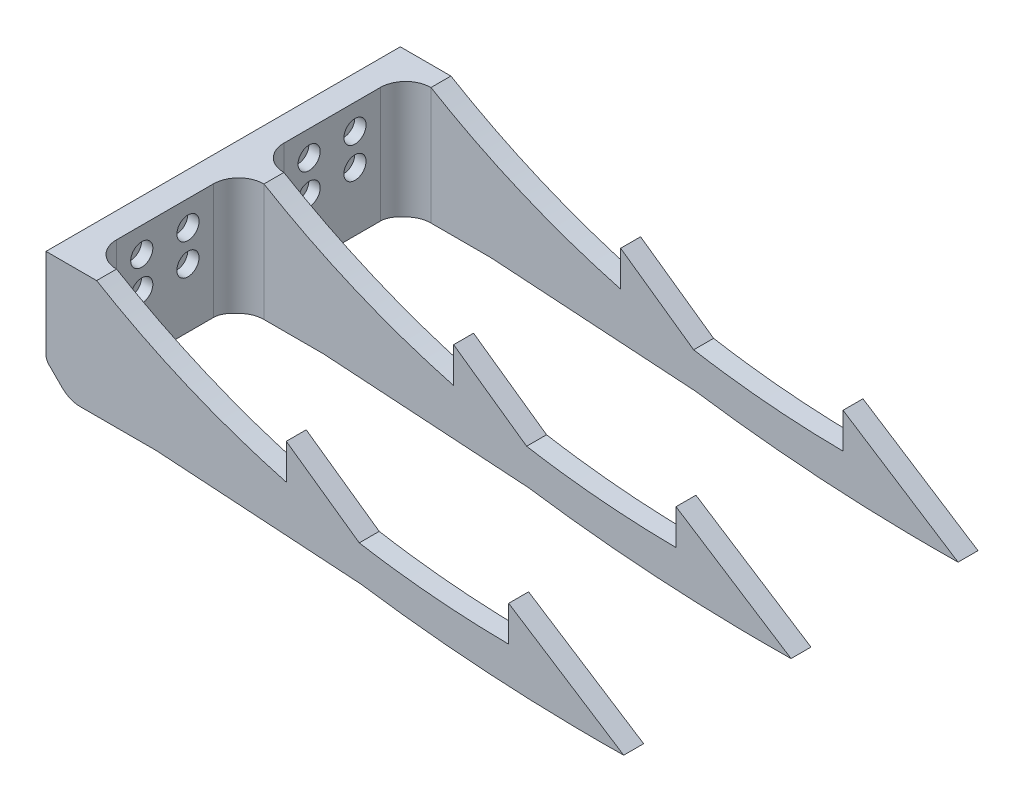
SolidWorks part; units mm, degrees
ref_plane "Front Plane" through (0, 0, 0) normal (0, 0, 1) x (1, 0, 0)
ref_plane "Top Plane" through (0, 0, 0) normal (0, 1, 0) x (1, 0, 0)
ref_plane "Right Plane" through (0, 0, 0) normal (1, 0, 0) x (0, 0, -1)
sketch "Sketch1" plane through (0, 0, 0) normal (0, 0, 1) x (1, 0, 0)
  line L0 (0, -6.35) -> (0, 6.35)
  line L1 (0, 6.35) -> (12.7, 6.35)
  line L2 (116.0939, -20.9749) -> (116.0939, -12.0849)
  line L3 (116.0939, -12.0849) -> (144.9605, -30.6605)
  line L4 (78.6103, -17.6935) -> (60.2919, -4.7804)
  line L5 (0, 12.7) -> (0, -12.7) construction
  line L6 (0, -12.7) -> (17.9605, -30.6605) construction
  line L7 (17.9605, -30.6605) -> (144.9605, -30.6605) construction
  line L8 (60.2919, -4.7804) -> (60.2919, -13.6704)
  spline S0 degree 2 poles (144.9605, -30.6605) (68.4115, -31.7178) (0, -6.35) knots 0 0 0 0.711551 0.711551 0.711551
  spline S1 degree 2 poles (116.0939, -20.9749) (96.6139, -20.8008) (78.6103, -17.6935) knots 0 0 0 0.222604 0.222604 0.222604
  spline S2 degree 3 poles (60.2919, -13.6704) (43.3593, -9.12) (27.4954, -2.4465) (12.7, 6.35) knots 0.338319 0.338319 0.338319 0.338319 0.666344 0.666344 0.666344 0.666344
  dimension "D1" = 12.7
  dimension "D2" = 12.7
  dimension "D3" = 8.89
  dimension "D4" = 8.89
  dimension "D6" = 25.4
  dimension "D8" = 25.4
  dimension "D9" = 127
extrude "Boss-Extrude1" add sketch "Sketch1" along normal blind 5
sketch "Sketch2" plane through (0, 0, 5) normal (0, 0, 1) x (1, 0, 0)
  line L0 (16.0704, -23.1077) -> (8.5569, -23.1077)
  line L1 (0, 6.35) -> (6.3316, 6.35)
  line L2 (0, 6.35) -> (0, -9.1178)
  line L3 (0, -9.1178) -> (0, -16.3764)
  line L4 (6.3316, 6.35) -> (6.3316, -8.6351)
  line L5 (27.6327, -23.1077) -> (16.0704, -23.1077)
  line L6 (6.3316, -8.6351) -> (13.8152, -11.1762)
  line L7 (4.0668, -21.2478) -> (0.6193, -17.8003)
  line L9 (79.2431, -26.4677) -> (27.6327, -23.1077)
  arc A0 (4.0668, -21.2478) -> (8.5569, -23.1077) centre (8.5569, -16.7577) ccw
  arc A2 (0, -16.3764) -> (0.6193, -17.8003) centre (2.5274, -16.1238) ccw
  parabola Q0 (13.8152, -11.1762) -> (79.2431, -26.4677) focus (76.8846, 170.0406) apex (20.4253, -13.2777)
  parabola Q1 (0, -6.35) -> (144.9605, -30.6605) focus (77.0052, 170.1195) apex (20.5192, -13.3081) construction
  parabola Q2 (0, -6.35) -> (144.9605, -30.6605) focus (77.0052, 170.1195) apex (20.5192, -13.3081) construction
  dimension "D2" = 6.35
extrude "Boss-Extrude2" add sketch "Sketch2" against normal blind 88.9
ref_plane "Plane1" through (0, 0, -39.45) normal (0, 0, 1) x (1, 0, 0)
mirror "Mirror1" about plane through (0, 0, -39.45) normal (0, 0, 1) of "Boss-Extrude1"
ref_plane "Plane2" through (0, 0, -18.495) normal (0, 0, 1) x (1, 0, 0)
mirror "Mirror3" about plane through (0, 0, -18.495) normal (0, 0, 1) of "Boss-Extrude1"
sketch "Sketch8" plane through (0, 6.35, 0) normal (0, 1, 0) x (1, 0, 0)
  line L0 (6.3316, 78.9) -> (84.5362, 78.9)
  line L1 (78.6103, 78.9) -> (116.0939, 78.9) construction
  line L2 (84.5362, 78.9) -> (84.5362, 41.99)
  line L3 (116.0939, 0) -> (78.6103, 0) construction
  line L4 (84.5362, 0) -> (6.3316, 0)
  line L5 (6.3316, 78.9) -> (6.3316, 41.99)
  line L6 (6.3316, 36.99) -> (84.5362, 36.99)
  line L7 (84.5362, 0) -> (84.5362, 36.99)
  line L8 (116.0939, 41.99) -> (78.6103, 41.99) construction
  line L9 (84.5362, 41.99) -> (6.3316, 41.99)
  line L10 (6.3316, 36.99) -> (6.3316, 0)
extrude "Cut-Extrude2" cut sketch "Sketch8" against normal blind 62.23
fillet "Fillet1" radius 6.35 9 edges at (6.3316, -8.1775, -36.99) (6.3316, -8.1775, -41.99) (7.4262, -23.0062, -78.9) (7.4262, -23.0062, -41.99) (7.4262, -23.0062, 0) (7.4262, -23.0062, -36.99) (6.3316, -8.1775, 0) (6.3316, -8.1775, -78.9)
hole_wizard "CBORE for #4 Socket Head Cap Screw1" positions "Sketch3" profile "Sketch4" counterbore size "#4" standard "ANSI Inch" end condition through all
sketch "Sketch3" plane through (6.3316, 15.3303, -39.45) normal (1, 0, 0) x (0, 0, -1)
  point P0 (-26.75, -23.2043)
  point P2 (-15.16, -15.3303)
  point P13 (15.24, -23.2043)
  point P15 (26.75, -15.3303)
  point P26 (-26.75, -15.3303)
  point P28 (-15.16, -23.2043)
  point P30 (15.24, -15.3303)
  point P32 (26.75, -23.2043)
sketch "Sketch4" plane through (6.3316, -7.874, -12.7) normal (0, 0, 1) x (0, 1, 0)
  line L0 (0, 0) -> (0, 6.3316)
  line L1 (0, 6.3316) -> (1.1303, 6.3316)
  line L2 (1.1303, 6.3316) -> (1.1303, 2.8448)
  line L3 (1.1303, 2.8448) -> (2.7788, 2.8448)
  line L4 (2.7788, 2.8448) -> (2.7788, 0)
  line L5 (2.7788, 0) -> (0, 0)
  line L6 (0, -6.35) -> (0, 107.95) construction
  dimension "Thru Hole Dia." = 2.2606
  dimension "Thru Hole Depth" = 6.3316
  dimension "C'Bore Dia." = 5.5575
  dimension "C'Bore Depth" = 2.8448
sketch "Sketch7" plane through (-1.9744, -5.8148, 0) normal (0.3215, 0.9469, 0) x (0.9469, -0.3215, 0)
  line L0 (8.7718, 30.64) -> (8.7718, 26.9625) construction
  line L1 (8.7718, 26.9625) -> (8.7718, 21.6175) construction
  line L2 (8.7718, 21.6175) -> (8.7718, 15.3725) construction
  line L3 (8.7718, 15.3725) -> (8.7718, 10.0275) construction
  line L4 (8.7718, 10.0275) -> (8.7718, 6.35) construction
  line L5 (83.5454, 0) -> (16.6753, 0) construction
  line L6 (16.6751, 0) -> (15.4779, 0) construction
  line L7 (83.5454, 36.99) -> (83.5454, 0) construction
  line L8 (16.6753, 36.99) -> (83.5454, 36.99) construction
  line L9 (16.6751, 36.99) -> (15.4779, 36.99) construction
  line L10 (8.7718, 30.64) -> (8.7718, 26.9625)
  line L11 (8.7718, 26.9625) -> (8.7718, 21.6175)
  line L12 (8.7718, 21.6175) -> (8.7718, 15.3725)
  line L13 (8.7718, 15.3725) -> (8.7718, 10.0275)
  line L14 (8.7718, 10.0275) -> (8.7718, 6.35)
  line L15 (83.5454, 0) -> (16.6753, 0)
  line L16 (16.6751, 0) -> (15.4779, 0)
  line L17 (83.5454, 36.99) -> (83.5454, 0)
  line L18 (16.6753, 36.99) -> (83.5454, 36.99)
  line L19 (16.6751, 36.99) -> (15.4779, 36.99)
  ellipse E0 centre (15.4779, 30.64) end of major axis (8.7718, 30.64) minor radius 6.35 (15.4779, 36.99) -> (8.7718, 30.64) ccw construction
  ellipse E1 centre (15.4779, 6.35) end of major axis (8.7718, 6.35) minor radius 6.35 (8.7718, 6.35) -> (15.4779, 0) ccw construction
  ellipse E2 centre (15.4779, 30.64) end of major axis (8.7718, 30.64) minor radius 6.35 (15.4779, 36.99) -> (8.7718, 30.64) ccw
  ellipse E3 centre (15.4779, 6.35) end of major axis (8.7718, 6.35) minor radius 6.35 (8.7718, 6.35) -> (15.4779, 0) ccw
